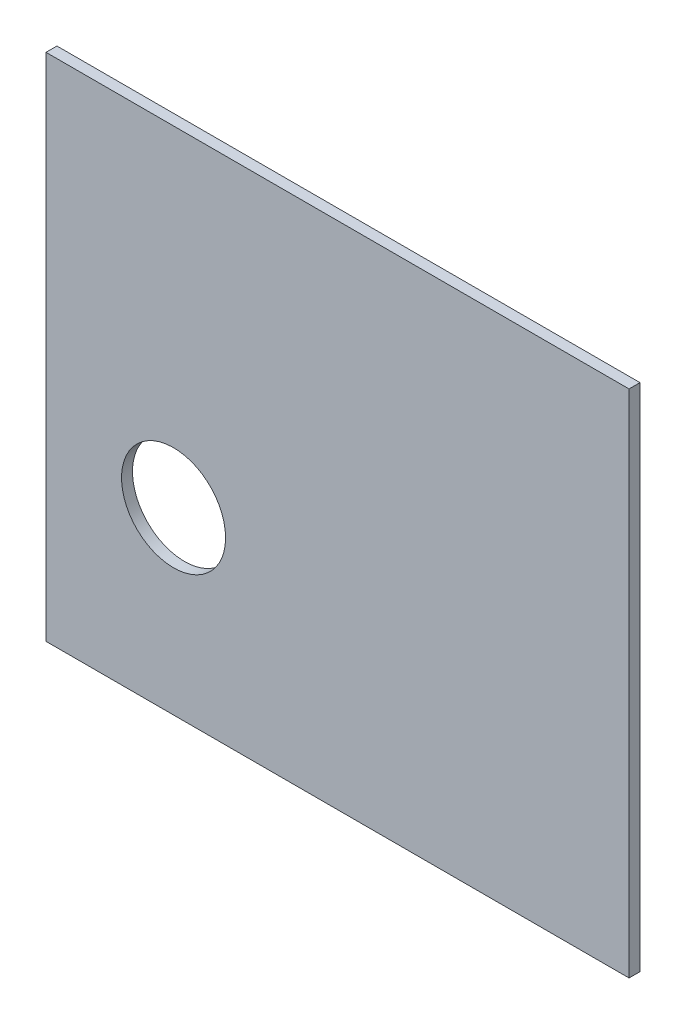
SolidWorks part; units mm, degrees
ref_plane "Front Plane" through (0, 0, 0) normal (0, 0, 1) x (1, 0, 0)
ref_plane "Top Plane" through (0, 0, 0) normal (0, 1, 0) x (1, 0, 0)
ref_plane "Right Plane" through (0, 0, 0) normal (1, 0, 0) x (0, 0, -1)
sketch "Sketch1" plane through (0, 0, 0) normal (0, 0, 1) x (1, 0, 0)
  line L1 (0, 0) -> (160, 0)
  line L2 (0, 0) -> (0, 140)
  line L3 (0, 140) -> (160, 140)
  line L4 (160, 0) -> (160, 140)
  dimension "D1" = 160
  dimension "D2" = 140
extrude "Boss-Extrude1" add sketch "Sketch1" along normal blind 3
sketch "Sketch2" plane through (0, 0, 3) normal (0, 0, 1) x (1, 0, 0)
  line L0 (160, 140) -> (0, 140) construction
  line L2 (0, 140) -> (0, 0) construction
  circle A0 centre (35, 49.26) radius 14.275
  point P2 (35, 99.4322)
  dimension "D1" = 28.55
  dimension "D2" = 35
  dimension "D3" = 90.74
extrude "Cut-Extrude1" cut sketch "Sketch2" against normal blind 3
